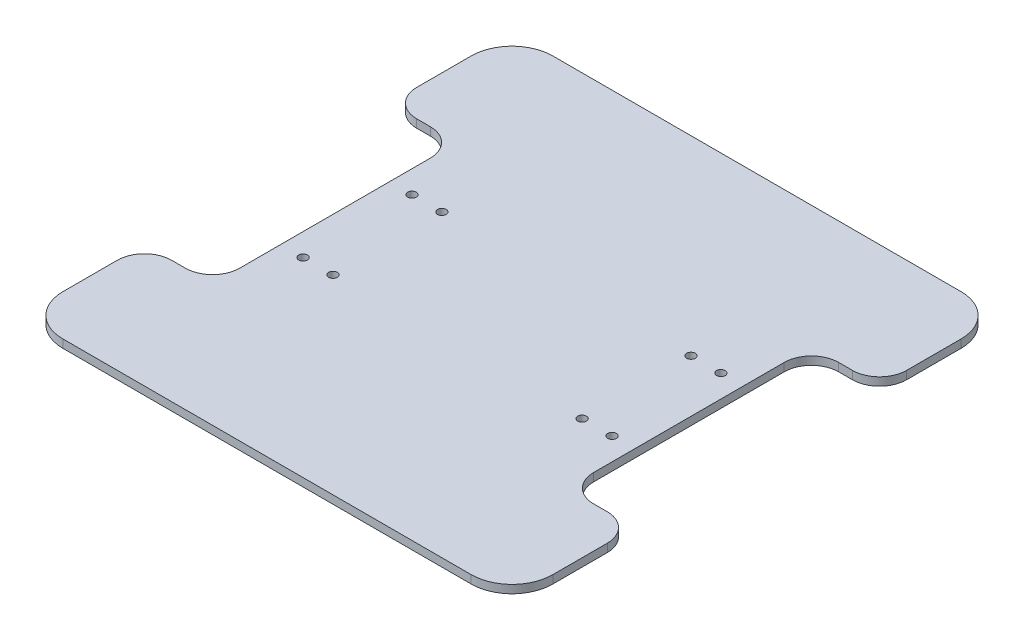
SolidWorks part; units mm, degrees
ref_plane "Спереди" through (0, 0, 0) normal (0, 0, 1) x (1, 0, 0)
ref_plane "Сверху" through (0, 0, 0) normal (0, 1, 0) x (1, 0, 0)
ref_plane "Справа" through (0, 0, 0) normal (1, 0, 0) x (0, 0, -1)
sketch "Sketch1" plane through (0, 0, 0) normal (0, 1, 0) x (1, 0, 0)
  line L1 (-90, 90) -> (90, 90)
  line L2 (-90, 90) -> (-90, -90)
  line L3 (-90, -90) -> (90, -90)
  line L4 (90, 90) -> (90, -90)
  line L5 (-90, 90) -> (90, -90) construction
  line L6 (-90, -90) -> (90, 90) construction
  point P0 (0, 0)
  dimension "D1" = 180
  dimension "D2" = 180
extrude "Boss-Extrude1" add sketch "Sketch1" along normal blind 3
fillet "Fillet1" radius 15 4 edges at (-90, 1.5, -90) (90, 1.5, -90) (-90, 1.5, 90) (90, 1.5, 90)
sketch "Sketch2" plane through (0, 3, 0) normal (0, 1, 0) x (1, 0, 0)
  line L0 (0, 0) -> (-77.5, 0) construction
  line L1 (2.75, 0) -> (-2.75, 0) construction
  line L2 (-90, 75) -> (-90, -75) construction
  line L3 (-90, 45) -> (-65, 45)
  line L4 (-90, 45) -> (-90, -45)
  line L5 (-90, -45) -> (-65, -45)
  line L6 (-65, 45) -> (-65, -45)
  line L7 (-90, 45) -> (-65, -45) construction
  line L8 (-90, -45) -> (-65, 45) construction
  line L9 (0, 0) -> (0, 45) construction
  line L10 (90, -45) -> (65, 45) construction
  line L11 (90, 45) -> (65, -45) construction
  line L12 (65, 45) -> (65, -45)
  line L13 (90, -45) -> (65, -45)
  line L14 (90, 45) -> (90, -45)
  line L15 (90, 45) -> (65, 45)
  circle A0 centre (-56.75, 20) radius 1.6
  circle A1 centre (-45.75, 20) radius 1.6
  circle A2 centre (-56.75, -20) radius 1.6
  circle A3 centre (-45.75, -20) radius 1.6
  circle A4 centre (45.75, 20) radius 1.6
  circle A5 centre (56.75, 20) radius 1.6
  circle A6 centre (45.75, -20) radius 1.6
  circle A7 centre (56.75, -20) radius 1.6
  dimension "D1" = 25
  dimension "D2" = 90
extrude "Cut-Extrude2" cut sketch "Sketch2" against normal through all
fillet "Fillet2" radius 10 8 edges at (-65, 1.5, 45) (-65, 1.5, -45) (65, 1.5, -45) (65, 1.5, 45) (90, 1.5, -45) (90, 1.5, 45) (-90, 1.5, 45) (-90, 1.5, -45)
